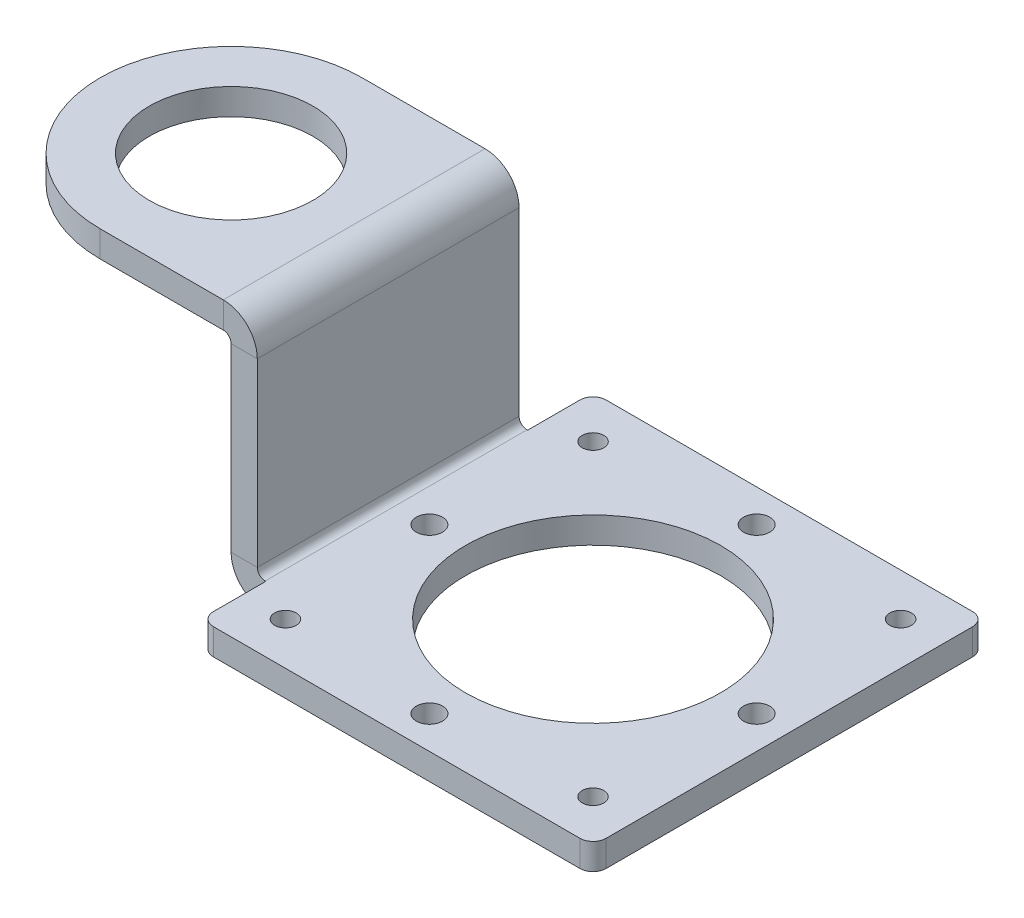
SolidWorks part; units mm, degrees
note: The reader was unsure of these and kept them because the rebuilt part matched: flange length of "Ребро-кромка1", "Ребро-кромка2".
ref_plane "Спереди" through (0, 0, 0) normal (0, 0, 1) x (1, 0, 0)
ref_plane "Сверху" through (0, 0, 0) normal (0, 1, 0) x (1, 0, 0)
ref_plane "Справа" through (0, 0, 0) normal (1, 0, 0) x (0, 0, -1)
sketch "Эскиз1" plane through (0, 0, 0) normal (0, 1, 0) x (1, 0, 0)
  line L0 (-9.0949, 33.781) -> (-9.0949, -26.219) construction
  line L1 (-39.0949, 33.781) -> (20.9051, 33.781)
  line L2 (-39.0949, 33.781) -> (-39.0949, -26.219)
  line L3 (-39.0949, -26.219) -> (20.9051, -26.219)
  line L4 (20.9051, 33.781) -> (20.9051, -26.219)
  line L5 (-9.0949, -26.219) -> (20.9051, 3.781) construction
  line L6 (20.9051, 3.781) -> (-39.0949, 3.781) construction
  line L7 (-32.5949, 27.281) -> (14.4051, 27.281) construction
  line L8 (14.4051, 27.281) -> (14.4051, -19.719) construction
  line L9 (14.4051, -19.719) -> (-32.5949, -19.719) construction
  line L10 (-32.5949, -19.719) -> (-32.5949, 27.281) construction
  circle A0 centre (-32.5949, 27.281) radius 1.65
  circle A1 centre (14.4051, 27.281) radius 1.65
  circle A2 centre (-32.5949, -19.719) radius 1.65
  circle A3 centre (14.4051, -19.719) radius 1.65
  circle A4 centre (-9.0949, 3.781) radius 19.5
  circle A5 centre (-34.0949, 3.781) radius 2
  circle A6 centre (15.9051, 3.781) radius 2
  circle A7 centre (-9.0949, 3.781) radius 25 construction
  circle A8 centre (-9.0949, 28.781) radius 2
  circle A9 centre (-9.0949, -21.219) radius 2
  dimension "D3" = 23.5
  dimension "D4" = 47
  dimension "D7" = 3.3
  dimension "D8" = 3.3
  dimension "D9" = 3.3
  dimension "D10" = 3.3
  dimension "D11" = 39
  dimension "D12" = 4
  dimension "D13" = 4
  dimension "D14" = 50
  dimension "D16" = 4
  dimension "D17" = 4
  dimension "D1" = 60
  dimension "D2" = 60
  dimension "D5" = 23.5
  dimension "D6" = 23.5
  dimension "D15" = 25
sheet metal parameters "Листовой металл1" thickness 4 parameters "D1"=1.2
base flange "Базовая кромка1" sketch "Эскиз1" thickness 4 reverse thickness direction no parameters "D1"=1.2
sketch "Эскиз4" plane through (-39.0949, 0, 0) normal (-1, 0, 0) x (0, 0, 1)
  line L0 (-33.781, 0) -> (26.219, 0) construction
  line L1 (-23.781, 0) -> (16.219, 0)
  line L2 (-23.781, 0) -> (-23.781, -4)
  line L3 (-23.781, -4) -> (16.219, -4)
  line L4 (16.219, 0) -> (16.219, -4)
  line L5 (-33.781, -4) -> (26.219, -4) construction
  line L6 (-33.781, -4) -> (-33.781, 0) construction
  line L7 (26.219, -4) -> (26.219, 0) construction
  point P8 (-33.781, -2)
  dimension "D1" = 10
  dimension "D2" = 10
extrude "Бобышка-Вытянуть1" add sketch "Эскиз4" along normal blind 0.1
edge flange "Ребро-кромка1" sketch "Эскиз7" flange angle 90 flange length 30 flange position bend outside bend radius 1.2 thickness 4 relief rectangular parameters "D6"=10
sketch "Эскиз7" plane through (-39.1949, 0, 0) normal (-1, 0, 0) x (0, 0, 1)
  line L0 (16.219, 0) -> (-23.781, 0) construction
  line L1 (16.219, 0) -> (-23.781, 0)
  line L2 (-23.781, 0) -> (-23.781, 30)
  line L3 (-23.781, 30) -> (16.219, 30)
  line L4 (16.219, 30) -> (16.219, 0)
bend "EdgeBend1" bend radius 1.2 bend angle 90 parameters "D5"=1
edge flange "Ребро-кромка2" sketch "Эскиз10" flange angle 90 flange length 40 flange position material outside bend radius 1.2 thickness 4 relief rectangular parameters "D6"=10
sketch "Эскиз10" plane through (-44.3949, 30, 0) normal (0, 1, 0) x (0, 0, -1)
  line L0 (-16.219, 0) -> (23.781, 0) construction
  line L1 (-16.219, 0) -> (23.781, 0)
  line L2 (-16.219, 0) -> (-16.219, 40)
  line L3 (-16.219, 40) -> (23.781, 40)
  line L4 (23.781, 40) -> (23.781, 0)
bend "EdgeBend2" bend radius 1.2 bend angle 90 parameters "D5"=2
fillet "Скругление1" radius 2 4 edges at (-39.0949, -2, -33.781) (20.9051, -2, -33.781) (20.9051, -2, 26.219) (-39.0949, -2, 26.219)
sketch "Эскиз11" plane through (0, 34, 0) normal (0, 1, 0) x (1, 0, 0)
  line L0 (-84.3949, 3.781) -> (-45.5949, 3.781) construction
  line L1 (-84.3949, 23.781) -> (-84.3949, -16.219) construction
  line L2 (-45.5949, 23.781) -> (-45.5949, -16.219) construction
  circle A0 centre (-64.3949, 3.781) radius 12.5
  dimension "D1" = 20
  dimension "D2" = 25
extrude "Вырез-Вытянуть1" cut sketch "Эскиз11" against normal blind 10 normal cut yes
fillet "Скругление2" radius 20 2 edges at (-84.3949, 32, -23.781) (-84.3949, 32, 16.219)
flat pattern "Развертка1" [suppressed]
sketch "Сгиб-Линии1" plane through (0, 0, 0) normal (0, 1, 0) x (1, 0, 0)
sketch3d "Граничная рамка1" [suppressed]
  line L0 (-20.9051, -26.219, 0) -> (39.0949, -26.219, 0) construction
  line L1 (-20.9051, 33.781, 0) -> (39.0949, 33.781, 0) construction
  line L2 (-20.9051, -26.219, 0) -> (-20.9051, 33.781, 0) construction
  line L3 (39.0949, -26.219, 0) -> (39.0949, 33.781, 0) construction
bend of the flat pattern "Плоское состояние-<EdgeBend1>1"
bend of the flat pattern "Плоское состояние-<EdgeBend2>1"
